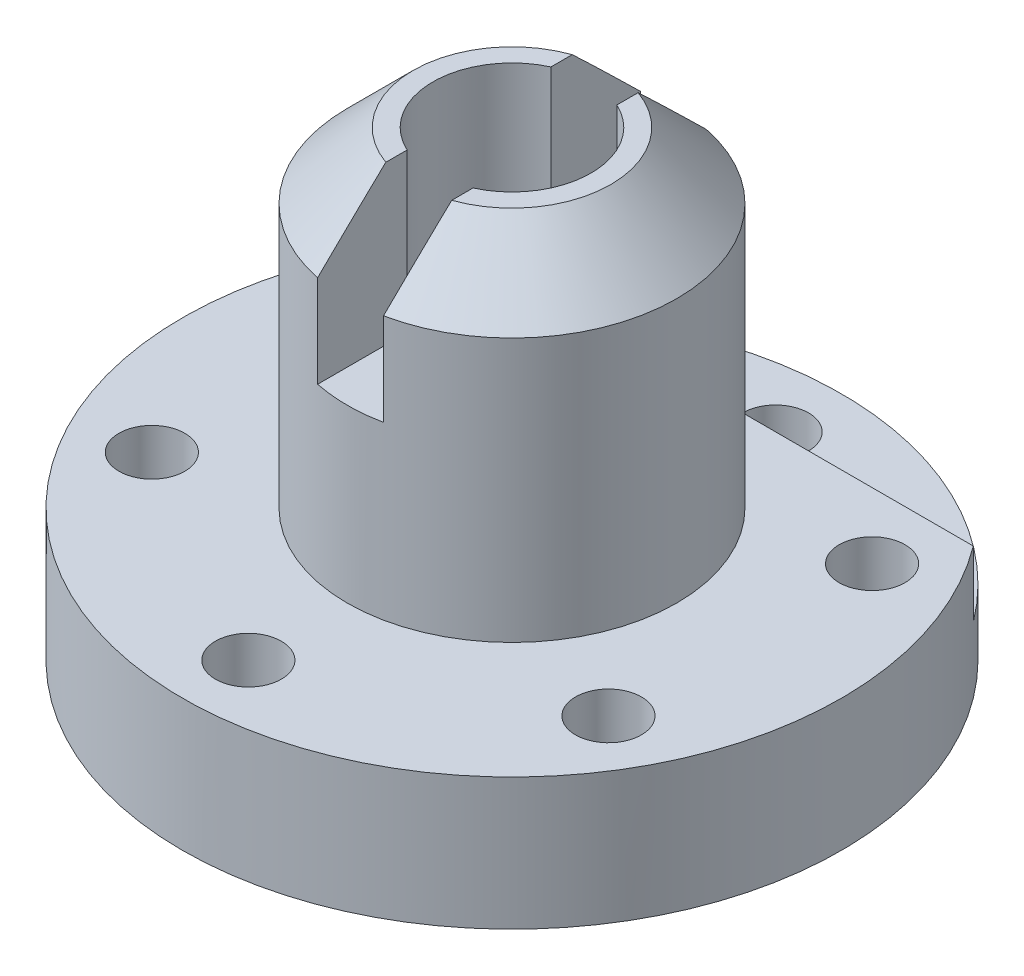
SolidWorks part; units mm, degrees
material "1060 Alloy"
ref_plane "Front Plane" through (0, 0, 0) normal (0, 0, 1) x (1, 0, 0)
ref_plane "Top Plane" through (0, 0, 0) normal (0, 1, 0) x (1, 0, 0)
ref_plane "Right Plane" through (0, 0, 0) normal (1, 0, 0) x (0, 0, -1)
sketch "Sketch1" plane through (0, 0, 0) normal (0, 1, 0) x (1, 0, 0)
  line L0 (-20, 15) -> (20, 15)
  circle A0 centre (0, 0) radius 25
  circle A1 centre (0, 0) radius 12.5
  circle A2 centre (0, 0) radius 6
  dimension "D1" = 50
  dimension "D2" = 25
  dimension "D3" = 12
  dimension "D4" = 15
extrude "Boss-Extrude1" add sketch "Sketch1" along normal blind 10 contours A0
extrude "Boss-Extrude2" add sketch "Sketch1<3>" along normal blind 35 contours A1 A2 region at (-12.1464, 0, 0)
sketch "Sketch1<3>" plane through (0, 0, 0) normal (0, 1, 0) x (1, 0, 0) same geometry as "Sketch1"
extrude "Cut-Extrude1" cut sketch "Sketch1<5>" along normal up to surface (10 mm away) from offset 5 contours L0 A0 region at (0, 0, -19.0776) up to face at (0, 10, 12.5)
sketch "Sketch1<5>" plane through (0, 0, 0) normal (0, 1, 0) x (1, 0, 0) same geometry as "Sketch1"
sketch "Sketch2" plane through (0, 0, 0) normal (0, 0, 1) x (1, 0, 0)
  line L0 (0, 35) -> (0, 0) construction
  line L1 (12.5, 35) -> (-12.5, 35) construction
  line L3 (-2.5, 23) -> (2.5, 23)
  line L4 (-2.5, 23) -> (-2.5, 35)
  line L5 (-2.5, 35) -> (2.5, 35)
  line L6 (2.5, 23) -> (2.5, 35)
  circle A0 centre (0, 23) radius 2.5
  dimension "D1" = 5
  dimension "D2" = 12
extrude "Cut-Extrude2" cut sketch "Sketch2" against normal through all both and the other way through all contours L0 L5 L4 A0 | L5 L0 A0 L6 | A0 L0 L3 | L0 A0 L3 region at (1.287, 29.9662, 0) region at (-1.287, 29.9662, 0) region at (1.061, 24.061, 0) region at (-1.061, 24.061, 0)
sketch "Sketch3" plane through (0, 0, 0) normal (0, 1, 0) x (1, 0, 0)
  line L0 (0, 0) -> (0, 28.2461) construction
  circle A0 centre (0, 20) radius 2.5
  dimension "D2" = 5
  dimension "D1" = 20
extrude "Cut-Extrude3" cut sketch "Sketch3" along normal through all contours A0
pattern_circular "CirPattern1" count 6 over 360 about axis through (0, 10, 0) along (0, 1, 0) of "Cut-Extrude3"
chamfer "Chamfer1" distance 5 angle 45 2 edges at (-12.5, 35, 0) (12.5, 35, 0)
sketch "Sketch4" [suppressed] plane through (0, 0, 0) normal (1, 0, 0) x (0, 0, -1)
  line L0 (0, 0) -> (0, 46.0964) construction
  circle A0 centre (0, 25) radius 5
  dimension "D2" = 10
  dimension "D1" = 25
extrude "Cut-Extrude4" [suppressed] cut sketch "Sketch4" against normal through all both and the other way through all
